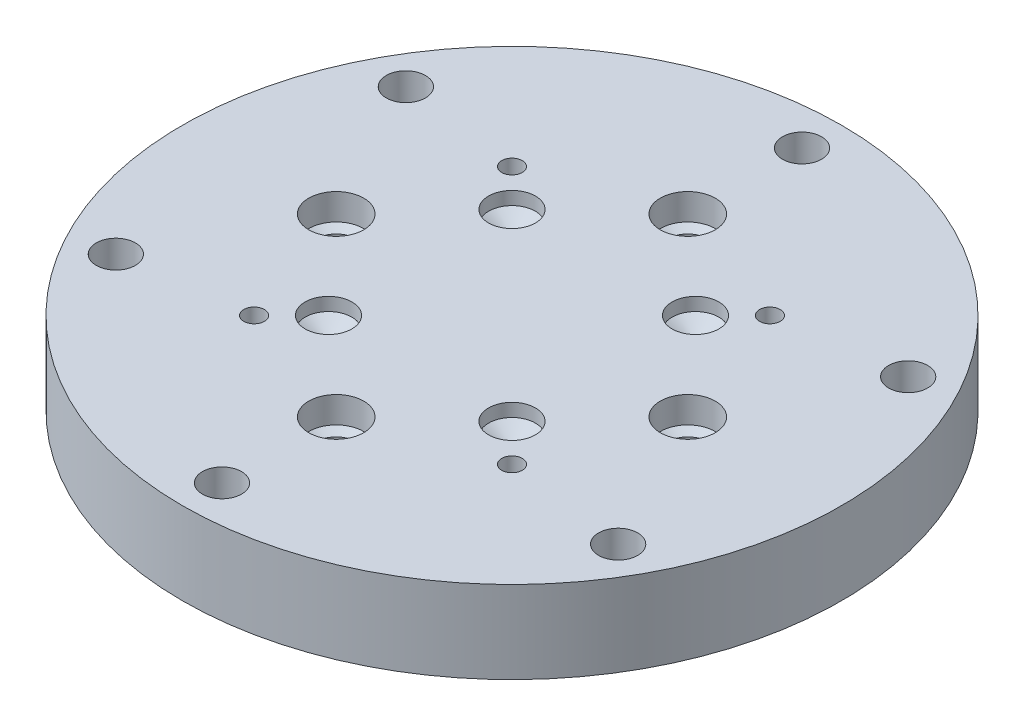
SolidWorks part; units mm, degrees
material "Copper"
ref_plane "Front Plane" through (0, 0, 0) normal (0, 0, 1) x (1, 0, 0)
ref_plane "Top Plane" through (0, 0, 0) normal (0, 1, 0) x (1, 0, 0)
ref_plane "Right Plane" through (0, 0, 0) normal (1, 0, 0) x (0, 0, -1)
ref_axis "Y Axis" through (0, 0.1588, 0) along (0, -1, 0)
sketch "outer" plane through (0, 0, 0) normal (0, 1, 0) x (1, 0, 0)
  circle A0 centre (0, 0) radius 19.05
  dimension "D1" = 38.1
extrude "Body" add sketch "outer" against normal blind 4.7625
sketch "Screw Position" plane through (0, 0, 0) normal (0, 1, 0) x (1, 0, 0)
  point P0 (0, -16.764)
  dimension "D1" = 16.764
hole_wizard "#4-40 Tapped Hole" positions "Sketch12" profile "Sketch13" tap size "#4-40" standard "ANSI Inch" end condition through all
sketch "Sketch12" plane through (0, 0, 0) normal (0, 1, 0) x (1, 0, 0)
  point P0 (0, -16.764)
sketch "Sketch13" plane through (0, 0, 16.764) normal (1, 0, 0) x (0, 0, 1)
  line L0 (0, 0) -> (0, 4.7625)
  line L1 (0, 4.7625) -> (1.1303, 4.7625)
  line L2 (1.1303, 4.7625) -> (1.1303, 0)
  line L5 (1.1303, 0) -> (0, 0)
  line L11 (0, -6.35) -> (0, 107.95) construction
  dimension "Thru Tap Drill Dia." = 2.2606
  dimension "Thru Tap Drill Depth" = 4.7625
cosmetic thread "Hole Thread3" parameters "D2"=2.8448
pattern_circular "Screw Holes" count 6 over 360 about axis through (0, 0.1588, 0) along (0, -1, 0) of "#4-40 Tapped Hole"
sketch "inner" plane through (0, 0, 0) normal (0, 1, 0) x (1, 0, 0)
  circle A0 centre (0, 0) radius 11.938
  dimension "D1" = 23.876
sketch "Inner Screw Position" plane through (0, 0, 0) normal (0, 1, 0) x (1, 0, 0)
  point P0 (-7.4536, 7.4536)
  dimension "D1" = 10.541
hole_wizard "#0-80 Tapped Hole" positions "Sketch34" profile "Sketch35" tap size "#0-80" standard "ANSI Inch" end condition through all
sketch "Sketch34" plane through (0, 0, 0) normal (0, 1, 0) x (1, 0, 0)
  point P0 (-7.4536, 7.4536)
sketch "Sketch35" plane through (-7.4536, 0, -7.4536) normal (1, 0, 0) x (0, 0, 1)
  line L0 (0, 0) -> (0, 4.7625)
  line L1 (0, 4.7625) -> (0.5956, 4.7625)
  line L2 (0.5956, 4.7625) -> (0.5956, 0)
  line L5 (0.5956, 0) -> (0, 0)
  line L11 (0, -6.35) -> (0, 107.95) construction
  dimension "Thru Tap Drill Dia." = 1.1913
  dimension "Thru Tap Drill Depth" = 4.7625
cosmetic thread "Hole Thread4" parameters "D2"=1.524
pattern_circular "Inner Screw Holes" count 4 over 360 about axis through (0, 0.1588, 0) along (0, -1, 0) of "#0-80 Tapped Hole"
sketch "IO Hole Location" plane through (0, 0, 0) normal (0, 1, 0) x (1, 0, 0)
  point P0 (0, 10.16)
hole_wizard "#43 (0.089) Diameter Hole1" positions "Sketch36" profile "Sketch37" hole size "#43" standard "ANSI Inch" end condition through all
sketch "Sketch36" plane through (0, 0, 0) normal (0, 1, 0) x (1, 0, 0)
  point P0 (0, 10.16)
sketch "Sketch37" plane through (0, 0, -10.16) normal (1, 0, 0) x (0, 0, 1)
  line L0 (0, 0) -> (0, 4.7625)
  line L1 (0, 4.7625) -> (1.1303, 4.7625)
  line L2 (1.1303, 4.7625) -> (1.1303, 0)
  line L5 (1.1303, 0) -> (0, 0)
  line L11 (0, -6.35) -> (0, 107.95) construction
  dimension "Thru Hole Dia." = 2.2606
  dimension "Thru Hole Depth" = 4.7625
hole_wizard "1/8 (0.125) Diameter Hole1" positions "Sketch38" profile "Sketch40" hole size "1/8" standard "ANSI Inch"
sketch "Sketch38" plane through (0, 0, 0) normal (0, 1, 0) x (1, 0, 0)
  point P0 (0, 10.16)
sketch "Sketch40" plane through (0, 0, -10.16) normal (1, 0, 0) x (0, 0, 1)
  line L0 (0, 0) -> (0, 2.4779)
  line L1 (0, 2.4779) -> (1.5875, 1.524)
  line L2 (1.5875, 1.524) -> (1.5875, 0)
  line L5 (1.5875, 0) -> (0, 0)
  line L10 (0, 2.4779) -> (-1.5875, 1.524) construction
  line L11 (0, -6.35) -> (0, 107.95) construction
  dimension "Hole Dia." = 3.175
  dimension "Hole Depth" = 1.524
  dimension "Drill Angle" = 118
hole_wizard "1/8 (0.125) Diameter Hole2" positions "Sketch41" profile "Sketch42" hole size "1/8" standard "ANSI Inch"
sketch "Sketch41" plane through (0, -4.7625, 0) normal (0, -1, 0) x (-1, 0, 0)
  point P0 (0, 10.16)
sketch "Sketch42" plane through (0, -4.7625, -10.16) normal (1, 0, 0) x (0, 0, -1)
  line L0 (0, 0) -> (0, 2.4779)
  line L1 (0, 2.4779) -> (1.5875, 1.524)
  line L2 (1.5875, 1.524) -> (1.5875, 0)
  line L5 (1.5875, 0) -> (0, 0)
  line L10 (0, 2.4779) -> (-1.5875, 1.524) construction
  line L11 (0, -6.35) -> (0, 107.95) construction
  dimension "Hole Dia." = 3.175
  dimension "Hole Depth" = 1.524
  dimension "Drill Angle" = 118
pattern_circular "IO Holes Pattern" count 4 over 360 about axis through (0, 0.1588, 0) along (0, -1, 0) of "#43 (0.089) Diameter Hole1", "1/8 (0.125) Diameter Hole1", "1/8 (0.125) Diameter Hole2"
sketch "Post Bottom Location" plane through (0, 0, 0) normal (0, 1, 0) x (1, 0, 0)
  point P0 (0, 7)
  point P1 (-5.3033, 5.3033)
  dimension "D1" = 7
  dimension "D2" = 7.5
hole_wizard "#36 (0.1065) Diameter Hole1" positions "Sketch44" profile "Sketch45" hole size "#36" standard "ANSI Inch"
sketch "Sketch44" plane through (0, 0, 0) normal (0, 1, 0) x (1, 0, 0)
  point P3 (-5.3033, 5.3033)
sketch "Sketch45" plane through (-5.3033, 0, -5.3033) normal (1, 0, 0) x (0, 0, 1)
  line L0 (0, 0) -> (0, 1.5747)
  line L1 (0, 1.5747) -> (1.3525, 0.762)
  line L2 (1.3525, 0.762) -> (1.3525, 0)
  line L5 (1.3525, 0) -> (0, 0)
  line L10 (0, 1.5747) -> (-1.3525, 0.762) construction
  line L11 (0, -6.35) -> (0, 107.95) construction
  dimension "Hole Dia." = 2.7051
  dimension "Hole Depth" = 0.762
  dimension "Drill Angle" = 118
pattern_circular "Post Bottoms" count 4 over 360 about axis through (0, 0.1588, 0) along (0, -1, 0) of "#36 (0.1065) Diameter Hole1"
equation "\"outer_d\"= 3 / 2in"
equation "\"screw_r\"= 0.66in"
equation "\"inner_d\"= 0.940in"
equation "\"bottom_h\"= 3 / 16in"
equation "\"pocket_h\"= 0.060in"
equation "\"screw_inner_r\"= 0.415in"
equation "\"io_r\"= 0.4in"
equation "\"D1@outer\" = \"outer_d\""
equation "\"D1@Body\" = \"bottom_h\""
equation "\"D1@inner\" = \"inner_d\""
equation "\"D1@Screw Position\" = \"screw_r\""
equation "\"D1@Inner Screw Position\" = \"screw_inner_r\""
equation "\"D1@IO Hole Location\"=\"io_r\""
equation "\"post_r1\"= 7mm"
equation "\"post_r2\"= 7.5mm"
equation "\"D1@Post Bottom Location\" = \"post_r1\""
equation "\"D2@Post Bottom Location\" = \"post_r2\""
equation "\"post_bottom_h\"= 0.03in"
